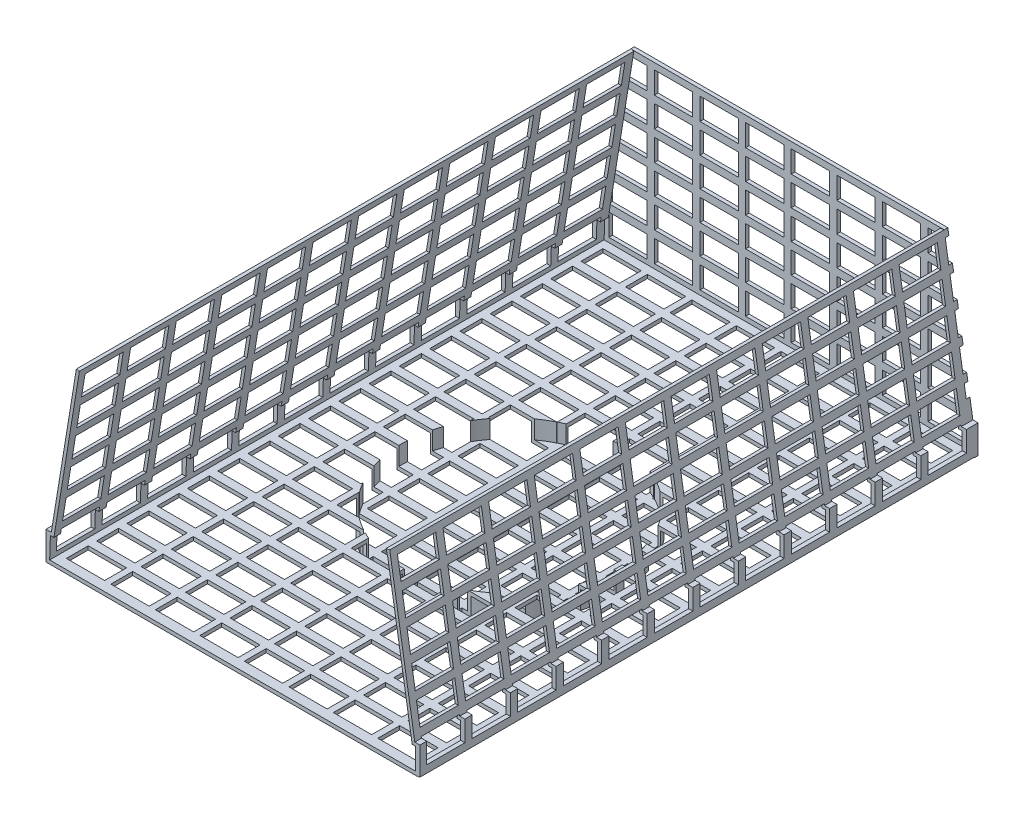
SolidWorks part; units mm, degrees
ref_plane "Front Plane" through (0, 0, 0) normal (0, 0, 1) x (1, 0, 0)
ref_plane "Top Plane" through (0, 0, 0) normal (0, 1, 0) x (1, 0, 0)
ref_plane "Right Plane" through (0, 0, 0) normal (1, 0, 0) x (0, 0, -1)
sketch "Sketch1" plane through (0, 0, 0) normal (0, 1, 0) x (1, 0, 0)
  line L1 (0, 0) -> (502.5, 0)
  line L2 (0, 0) -> (0, 760)
  line L3 (0, 760) -> (502.5, 760)
  line L4 (502.5, 0) -> (502.5, 760)
  dimension "D1" = 760
  dimension "D2" = 502.5
extrude "Boss-Extrude1" add sketch "Sketch1" against normal blind 5
sketch "Sketch2" plane through (0, 0, 0) normal (0, 1, 0) x (1, 0, 0)
  circle A0 centre (250.85, 380) radius 150
  dimension "D1" = 300
extrude "Boss-Extrude2" add sketch "Sketch2" against normal blind 30
sketch "Sketch3" plane through (0, 0, 0) normal (0, 1, 0) x (1, 0, 0)
  circle A0 centre (250.85, 380) radius 147.5
  dimension "D1" = 295
extrude "Cut-Extrude1" cut sketch "Sketch3" against normal blind 25
sketch "Sketch4" plane through (0, 0, -760) normal (0, 0, -1) x (-1, 0, 0)
  line L1 (-502.5, -5) -> (0, -5)
  line L2 (-502.5, -5) -> (-502.5, 245)
  line L3 (-502.5, 245) -> (0, 245)
  line L4 (0, -5) -> (0, 245)
  dimension "D1" = 250
extrude "Boss-Extrude3" add sketch "Sketch4" along normal blind 5
sketch "Sketch5" plane through (502.5, 0, 0) normal (1, 0, 0) x (0, 0, -1)
  line L1 (0, -5) -> (765, -5)
  line L2 (0, -5) -> (0, 245)
  line L3 (0, 245) -> (765, 245)
  line L4 (765, -5) -> (765, 245)
extrude "Boss-Extrude4" add sketch "Sketch5" along normal blind 5 and the other way blind 100
sketch "Sketch6" plane through (0, 0, 0) normal (-1, 0, 0) x (0, 0, 1)
  line L1 (0, -5) -> (-765, -5)
  line L2 (0, -5) -> (0, 245)
  line L3 (0, 245) -> (-765, 245)
  line L4 (-765, -5) -> (-765, 245)
extrude "Boss-Extrude5" add sketch "Sketch6" along normal blind 5 and the other way blind 100
sketch "Sketch7" plane through (507.5, 0, 0) normal (1, 0, 0) x (0, 0, -1)
  line L0 (71.6149, 235.9398) -> (124.1149, 235.9398)
  line L1 (9.1149, 235.9398) -> (61.6149, 235.9398)
  line L2 (9.1149, 235.9398) -> (9.1149, 205.9398)
  line L3 (9.1149, 205.9398) -> (61.6149, 205.9398)
  line L4 (61.6149, 235.9398) -> (61.6149, 205.9398)
  line L5 (71.6149, 235.9398) -> (71.6149, 205.9398)
  line L6 (71.6149, 205.9398) -> (124.1149, 205.9398)
  line L7 (124.1149, 235.9398) -> (124.1149, 205.9398)
  line L8 (134.1149, 235.9398) -> (186.6149, 235.9398)
  line L9 (134.1149, 235.9398) -> (134.1149, 205.9398)
  line L10 (134.1149, 205.9398) -> (186.6149, 205.9398)
  line L11 (186.6149, 235.9398) -> (186.6149, 205.9398)
  line L12 (196.6149, 235.9398) -> (249.1149, 235.9398)
  line L13 (196.6149, 235.9398) -> (196.6149, 205.9398)
  line L14 (196.6149, 205.9398) -> (249.1149, 205.9398)
  line L15 (249.1149, 235.9398) -> (249.1149, 205.9398)
  line L16 (259.1149, 235.9398) -> (311.6149, 235.9398)
  line L17 (259.1149, 235.9398) -> (259.1149, 205.9398)
  line L18 (259.1149, 205.9398) -> (311.6149, 205.9398)
  line L19 (311.6149, 235.9398) -> (311.6149, 205.9398)
  line L20 (321.6149, 235.9398) -> (374.1149, 235.9398)
  line L21 (321.6149, 235.9398) -> (321.6149, 205.9398)
  line L22 (321.6149, 205.9398) -> (374.1149, 205.9398)
  line L23 (374.1149, 235.9398) -> (374.1149, 205.9398)
  line L24 (384.1149, 235.9398) -> (436.6149, 235.9398)
  line L25 (384.1149, 235.9398) -> (384.1149, 205.9398)
  line L26 (384.1149, 205.9398) -> (436.6149, 205.9398)
  line L27 (436.6149, 235.9398) -> (436.6149, 205.9398)
  line L28 (446.6149, 235.9398) -> (499.1149, 235.9398)
  line L29 (446.6149, 235.9398) -> (446.6149, 205.9398)
  line L30 (446.6149, 205.9398) -> (499.1149, 205.9398)
  line L31 (499.1149, 235.9398) -> (499.1149, 205.9398)
  line L32 (509.1149, 235.9398) -> (561.6149, 235.9398)
  line L33 (509.1149, 235.9398) -> (509.1149, 205.9398)
  line L34 (509.1149, 205.9398) -> (561.6149, 205.9398)
  line L35 (561.6149, 235.9398) -> (561.6149, 205.9398)
  line L36 (571.6149, 235.9398) -> (624.1149, 235.9398)
  line L37 (571.6149, 235.9398) -> (571.6149, 205.9398)
  line L38 (571.6149, 205.9398) -> (624.1149, 205.9398)
  line L39 (624.1149, 235.9398) -> (624.1149, 205.9398)
  line L40 (634.1149, 235.9398) -> (686.6149, 235.9398)
  line L41 (634.1149, 235.9398) -> (634.1149, 205.9398)
  line L42 (634.1149, 205.9398) -> (686.6149, 205.9398)
  line L43 (686.6149, 235.9398) -> (686.6149, 205.9398)
  line L44 (696.6149, 235.9398) -> (749.1149, 235.9398)
  line L45 (696.6149, 235.9398) -> (696.6149, 205.9398)
  line L46 (696.6149, 205.9398) -> (749.1149, 205.9398)
  line L47 (749.1149, 235.9398) -> (749.1149, 205.9398)
  line L48 (71.6149, 195.9398) -> (124.1149, 195.9398)
  line L49 (9.1149, 195.9398) -> (61.6149, 195.9398)
  line L50 (9.1149, 195.9398) -> (9.1149, 165.9398)
  line L51 (9.1149, 165.9398) -> (61.6149, 165.9398)
  line L52 (61.6149, 195.9398) -> (61.6149, 165.9398)
  line L53 (71.6149, 195.9398) -> (71.6149, 165.9398)
  line L54 (71.6149, 165.9398) -> (124.1149, 165.9398)
  line L55 (124.1149, 195.9398) -> (124.1149, 165.9398)
  line L56 (134.1149, 195.9398) -> (186.6149, 195.9398)
  line L57 (134.1149, 195.9398) -> (134.1149, 165.9398)
  line L58 (134.1149, 165.9398) -> (186.6149, 165.9398)
  line L59 (186.6149, 195.9398) -> (186.6149, 165.9398)
  line L60 (196.6149, 195.9398) -> (249.1149, 195.9398)
  line L61 (196.6149, 195.9398) -> (196.6149, 165.9398)
  line L62 (196.6149, 165.9398) -> (249.1149, 165.9398)
  line L63 (249.1149, 195.9398) -> (249.1149, 165.9398)
  line L64 (259.1149, 195.9398) -> (311.6149, 195.9398)
  line L65 (259.1149, 195.9398) -> (259.1149, 165.9398)
  line L66 (259.1149, 165.9398) -> (311.6149, 165.9398)
  line L67 (311.6149, 195.9398) -> (311.6149, 165.9398)
  line L68 (321.6149, 195.9398) -> (374.1149, 195.9398)
  line L69 (321.6149, 195.9398) -> (321.6149, 165.9398)
  line L70 (321.6149, 165.9398) -> (374.1149, 165.9398)
  line L71 (374.1149, 195.9398) -> (374.1149, 165.9398)
  line L72 (384.1149, 195.9398) -> (436.6149, 195.9398)
  line L73 (384.1149, 195.9398) -> (384.1149, 165.9398)
  line L74 (384.1149, 165.9398) -> (436.6149, 165.9398)
  line L75 (436.6149, 195.9398) -> (436.6149, 165.9398)
  line L76 (446.6149, 195.9398) -> (499.1149, 195.9398)
  line L77 (446.6149, 195.9398) -> (446.6149, 165.9398)
  line L78 (446.6149, 165.9398) -> (499.1149, 165.9398)
  line L79 (499.1149, 195.9398) -> (499.1149, 165.9398)
  line L80 (509.1149, 195.9398) -> (561.6149, 195.9398)
  line L81 (509.1149, 195.9398) -> (509.1149, 165.9398)
  line L82 (509.1149, 165.9398) -> (561.6149, 165.9398)
  line L83 (561.6149, 195.9398) -> (561.6149, 165.9398)
  line L84 (571.6149, 195.9398) -> (624.1149, 195.9398)
  line L85 (571.6149, 195.9398) -> (571.6149, 165.9398)
  line L86 (571.6149, 165.9398) -> (624.1149, 165.9398)
  line L87 (624.1149, 195.9398) -> (624.1149, 165.9398)
  line L88 (634.1149, 195.9398) -> (686.6149, 195.9398)
  line L89 (634.1149, 195.9398) -> (634.1149, 165.9398)
  line L90 (634.1149, 165.9398) -> (686.6149, 165.9398)
  line L91 (686.6149, 195.9398) -> (686.6149, 165.9398)
  line L92 (696.6149, 195.9398) -> (749.1149, 195.9398)
  line L93 (696.6149, 195.9398) -> (696.6149, 165.9398)
  line L94 (696.6149, 165.9398) -> (749.1149, 165.9398)
  line L95 (749.1149, 195.9398) -> (749.1149, 165.9398)
  line L96 (71.6149, 155.9398) -> (124.1149, 155.9398)
  line L97 (9.1149, 155.9398) -> (61.6149, 155.9398)
  line L98 (9.1149, 155.9398) -> (9.1149, 125.9398)
  line L99 (9.1149, 125.9398) -> (61.6149, 125.9398)
  line L100 (61.6149, 155.9398) -> (61.6149, 125.9398)
  line L101 (71.6149, 155.9398) -> (71.6149, 125.9398)
  line L102 (71.6149, 125.9398) -> (124.1149, 125.9398)
  line L103 (124.1149, 155.9398) -> (124.1149, 125.9398)
  line L104 (134.1149, 155.9398) -> (186.6149, 155.9398)
  line L105 (134.1149, 155.9398) -> (134.1149, 125.9398)
  line L106 (134.1149, 125.9398) -> (186.6149, 125.9398)
  line L107 (186.6149, 155.9398) -> (186.6149, 125.9398)
  line L108 (196.6149, 155.9398) -> (249.1149, 155.9398)
  line L109 (196.6149, 155.9398) -> (196.6149, 125.9398)
  line L110 (196.6149, 125.9398) -> (249.1149, 125.9398)
  line L111 (249.1149, 155.9398) -> (249.1149, 125.9398)
  line L112 (259.1149, 155.9398) -> (311.6149, 155.9398)
  line L113 (259.1149, 155.9398) -> (259.1149, 125.9398)
  line L114 (259.1149, 125.9398) -> (311.6149, 125.9398)
  line L115 (311.6149, 155.9398) -> (311.6149, 125.9398)
  line L116 (321.6149, 155.9398) -> (374.1149, 155.9398)
  line L117 (321.6149, 155.9398) -> (321.6149, 125.9398)
  line L118 (321.6149, 125.9398) -> (374.1149, 125.9398)
  line L119 (374.1149, 155.9398) -> (374.1149, 125.9398)
  line L120 (384.1149, 155.9398) -> (436.6149, 155.9398)
  line L121 (384.1149, 155.9398) -> (384.1149, 125.9398)
  line L122 (384.1149, 125.9398) -> (436.6149, 125.9398)
  line L123 (436.6149, 155.9398) -> (436.6149, 125.9398)
  line L124 (446.6149, 155.9398) -> (499.1149, 155.9398)
  line L125 (446.6149, 155.9398) -> (446.6149, 125.9398)
  line L126 (446.6149, 125.9398) -> (499.1149, 125.9398)
  line L127 (499.1149, 155.9398) -> (499.1149, 125.9398)
  line L128 (509.1149, 155.9398) -> (561.6149, 155.9398)
  line L129 (509.1149, 155.9398) -> (509.1149, 125.9398)
  line L130 (509.1149, 125.9398) -> (561.6149, 125.9398)
  line L131 (561.6149, 155.9398) -> (561.6149, 125.9398)
  line L132 (571.6149, 155.9398) -> (624.1149, 155.9398)
  line L133 (571.6149, 155.9398) -> (571.6149, 125.9398)
  line L134 (571.6149, 125.9398) -> (624.1149, 125.9398)
  line L135 (624.1149, 155.9398) -> (624.1149, 125.9398)
  line L136 (634.1149, 155.9398) -> (686.6149, 155.9398)
  line L137 (634.1149, 155.9398) -> (634.1149, 125.9398)
  line L138 (634.1149, 125.9398) -> (686.6149, 125.9398)
  line L139 (686.6149, 155.9398) -> (686.6149, 125.9398)
  line L140 (696.6149, 155.9398) -> (749.1149, 155.9398)
  line L141 (696.6149, 155.9398) -> (696.6149, 125.9398)
  line L142 (696.6149, 125.9398) -> (749.1149, 125.9398)
  line L143 (749.1149, 155.9398) -> (749.1149, 125.9398)
  line L144 (71.6149, 115.9398) -> (124.1149, 115.9398)
  line L145 (9.1149, 115.9398) -> (61.6149, 115.9398)
  line L146 (9.1149, 115.9398) -> (9.1149, 85.9398)
  line L147 (9.1149, 85.9398) -> (61.6149, 85.9398)
  line L148 (61.6149, 115.9398) -> (61.6149, 85.9398)
  line L149 (71.6149, 115.9398) -> (71.6149, 85.9398)
  line L150 (71.6149, 85.9398) -> (124.1149, 85.9398)
  line L151 (124.1149, 115.9398) -> (124.1149, 85.9398)
  line L152 (134.1149, 115.9398) -> (186.6149, 115.9398)
  line L153 (134.1149, 115.9398) -> (134.1149, 85.9398)
  line L154 (134.1149, 85.9398) -> (186.6149, 85.9398)
  line L155 (186.6149, 115.9398) -> (186.6149, 85.9398)
  line L156 (196.6149, 115.9398) -> (249.1149, 115.9398)
  line L157 (196.6149, 115.9398) -> (196.6149, 85.9398)
  line L158 (196.6149, 85.9398) -> (249.1149, 85.9398)
  line L159 (249.1149, 115.9398) -> (249.1149, 85.9398)
  line L160 (259.1149, 115.9398) -> (311.6149, 115.9398)
  line L161 (259.1149, 115.9398) -> (259.1149, 85.9398)
  line L162 (259.1149, 85.9398) -> (311.6149, 85.9398)
  line L163 (311.6149, 115.9398) -> (311.6149, 85.9398)
  line L164 (321.6149, 115.9398) -> (374.1149, 115.9398)
  line L165 (321.6149, 115.9398) -> (321.6149, 85.9398)
  line L166 (321.6149, 85.9398) -> (374.1149, 85.9398)
  line L167 (374.1149, 115.9398) -> (374.1149, 85.9398)
  line L168 (384.1149, 115.9398) -> (436.6149, 115.9398)
  line L169 (384.1149, 115.9398) -> (384.1149, 85.9398)
  line L170 (384.1149, 85.9398) -> (436.6149, 85.9398)
  line L171 (436.6149, 115.9398) -> (436.6149, 85.9398)
  line L172 (446.6149, 115.9398) -> (499.1149, 115.9398)
  line L173 (446.6149, 115.9398) -> (446.6149, 85.9398)
  line L174 (446.6149, 85.9398) -> (499.1149, 85.9398)
  line L175 (499.1149, 115.9398) -> (499.1149, 85.9398)
  line L176 (509.1149, 115.9398) -> (561.6149, 115.9398)
  line L177 (509.1149, 115.9398) -> (509.1149, 85.9398)
  line L178 (509.1149, 85.9398) -> (561.6149, 85.9398)
  line L179 (561.6149, 115.9398) -> (561.6149, 85.9398)
  line L180 (571.6149, 115.9398) -> (624.1149, 115.9398)
  line L181 (571.6149, 115.9398) -> (571.6149, 85.9398)
  line L182 (571.6149, 85.9398) -> (624.1149, 85.9398)
  line L183 (624.1149, 115.9398) -> (624.1149, 85.9398)
  line L184 (634.1149, 115.9398) -> (686.6149, 115.9398)
  line L185 (634.1149, 115.9398) -> (634.1149, 85.9398)
  line L186 (634.1149, 85.9398) -> (686.6149, 85.9398)
  line L187 (686.6149, 115.9398) -> (686.6149, 85.9398)
  line L188 (696.6149, 115.9398) -> (749.1149, 115.9398)
  line L189 (696.6149, 115.9398) -> (696.6149, 85.9398)
  line L190 (696.6149, 85.9398) -> (749.1149, 85.9398)
  line L191 (749.1149, 115.9398) -> (749.1149, 85.9398)
  line L192 (71.6149, 75.9398) -> (124.1149, 75.9398)
  line L193 (9.1149, 75.9398) -> (61.6149, 75.9398)
  line L194 (9.1149, 75.9398) -> (9.1149, 45.9398)
  line L195 (9.1149, 45.9398) -> (61.6149, 45.9398)
  line L196 (61.6149, 75.9398) -> (61.6149, 45.9398)
  line L197 (71.6149, 75.9398) -> (71.6149, 45.9398)
  line L198 (71.6149, 45.9398) -> (124.1149, 45.9398)
  line L199 (124.1149, 75.9398) -> (124.1149, 45.9398)
  line L200 (134.1149, 75.9398) -> (186.6149, 75.9398)
  line L201 (134.1149, 75.9398) -> (134.1149, 45.9398)
  line L202 (134.1149, 45.9398) -> (186.6149, 45.9398)
  line L203 (186.6149, 75.9398) -> (186.6149, 45.9398)
  line L204 (196.6149, 75.9398) -> (249.1149, 75.9398)
  line L205 (196.6149, 75.9398) -> (196.6149, 45.9398)
  line L206 (196.6149, 45.9398) -> (249.1149, 45.9398)
  line L207 (249.1149, 75.9398) -> (249.1149, 45.9398)
  line L208 (259.1149, 75.9398) -> (311.6149, 75.9398)
  line L209 (259.1149, 75.9398) -> (259.1149, 45.9398)
  line L210 (259.1149, 45.9398) -> (311.6149, 45.9398)
  line L211 (311.6149, 75.9398) -> (311.6149, 45.9398)
  line L212 (321.6149, 75.9398) -> (374.1149, 75.9398)
  line L213 (321.6149, 75.9398) -> (321.6149, 45.9398)
  line L214 (321.6149, 45.9398) -> (374.1149, 45.9398)
  line L215 (374.1149, 75.9398) -> (374.1149, 45.9398)
  line L216 (384.1149, 75.9398) -> (436.6149, 75.9398)
  line L217 (384.1149, 75.9398) -> (384.1149, 45.9398)
  line L218 (384.1149, 45.9398) -> (436.6149, 45.9398)
  line L219 (436.6149, 75.9398) -> (436.6149, 45.9398)
  line L220 (446.6149, 75.9398) -> (499.1149, 75.9398)
  line L221 (446.6149, 75.9398) -> (446.6149, 45.9398)
  line L222 (446.6149, 45.9398) -> (499.1149, 45.9398)
  line L223 (499.1149, 75.9398) -> (499.1149, 45.9398)
  line L224 (509.1149, 75.9398) -> (561.6149, 75.9398)
  line L225 (509.1149, 75.9398) -> (509.1149, 45.9398)
  line L226 (509.1149, 45.9398) -> (561.6149, 45.9398)
  line L227 (561.6149, 75.9398) -> (561.6149, 45.9398)
  line L228 (571.6149, 75.9398) -> (624.1149, 75.9398)
  line L229 (571.6149, 75.9398) -> (571.6149, 45.9398)
  line L230 (571.6149, 45.9398) -> (624.1149, 45.9398)
  line L231 (624.1149, 75.9398) -> (624.1149, 45.9398)
  line L232 (634.1149, 75.9398) -> (686.6149, 75.9398)
  line L233 (634.1149, 75.9398) -> (634.1149, 45.9398)
  line L234 (634.1149, 45.9398) -> (686.6149, 45.9398)
  line L235 (686.6149, 75.9398) -> (686.6149, 45.9398)
  line L236 (696.6149, 75.9398) -> (749.1149, 75.9398)
  line L237 (696.6149, 75.9398) -> (696.6149, 45.9398)
  line L238 (696.6149, 45.9398) -> (749.1149, 45.9398)
  line L239 (749.1149, 75.9398) -> (749.1149, 45.9398)
  line L240 (71.6149, 35.9398) -> (124.1149, 35.9398)
  line L241 (9.1149, 35.9398) -> (61.6149, 35.9398)
  line L242 (9.1149, 35.9398) -> (9.1149, 5.9398)
  line L243 (9.1149, 5.9398) -> (61.6149, 5.9398)
  line L244 (61.6149, 35.9398) -> (61.6149, 5.9398)
  line L245 (71.6149, 35.9398) -> (71.6149, 5.9398)
  line L246 (71.6149, 5.9398) -> (124.1149, 5.9398)
  line L247 (124.1149, 35.9398) -> (124.1149, 5.9398)
  line L248 (134.1149, 35.9398) -> (186.6149, 35.9398)
  line L249 (134.1149, 35.9398) -> (134.1149, 5.9398)
  line L250 (134.1149, 5.9398) -> (186.6149, 5.9398)
  line L251 (186.6149, 35.9398) -> (186.6149, 5.9398)
  line L252 (196.6149, 35.9398) -> (249.1149, 35.9398)
  line L253 (196.6149, 35.9398) -> (196.6149, 5.9398)
  line L254 (196.6149, 5.9398) -> (249.1149, 5.9398)
  line L255 (249.1149, 35.9398) -> (249.1149, 5.9398)
  line L256 (259.1149, 35.9398) -> (311.6149, 35.9398)
  line L257 (259.1149, 35.9398) -> (259.1149, 5.9398)
  line L258 (259.1149, 5.9398) -> (311.6149, 5.9398)
  line L259 (311.6149, 35.9398) -> (311.6149, 5.9398)
  line L260 (321.6149, 35.9398) -> (374.1149, 35.9398)
  line L261 (321.6149, 35.9398) -> (321.6149, 5.9398)
  line L262 (321.6149, 5.9398) -> (374.1149, 5.9398)
  line L263 (374.1149, 35.9398) -> (374.1149, 5.9398)
  line L264 (384.1149, 35.9398) -> (436.6149, 35.9398)
  line L265 (384.1149, 35.9398) -> (384.1149, 5.9398)
  line L266 (384.1149, 5.9398) -> (436.6149, 5.9398)
  line L267 (436.6149, 35.9398) -> (436.6149, 5.9398)
  line L268 (446.6149, 35.9398) -> (499.1149, 35.9398)
  line L269 (446.6149, 35.9398) -> (446.6149, 5.9398)
  line L270 (446.6149, 5.9398) -> (499.1149, 5.9398)
  line L271 (499.1149, 35.9398) -> (499.1149, 5.9398)
  line L272 (509.1149, 35.9398) -> (561.6149, 35.9398)
  line L273 (509.1149, 35.9398) -> (509.1149, 5.9398)
  line L274 (509.1149, 5.9398) -> (561.6149, 5.9398)
  line L275 (561.6149, 35.9398) -> (561.6149, 5.9398)
  line L276 (571.6149, 35.9398) -> (624.1149, 35.9398)
  line L277 (571.6149, 35.9398) -> (571.6149, 5.9398)
  line L278 (571.6149, 5.9398) -> (624.1149, 5.9398)
  line L279 (624.1149, 35.9398) -> (624.1149, 5.9398)
  line L280 (634.1149, 35.9398) -> (686.6149, 35.9398)
  line L281 (634.1149, 35.9398) -> (634.1149, 5.9398)
  line L282 (634.1149, 5.9398) -> (686.6149, 5.9398)
  line L283 (686.6149, 35.9398) -> (686.6149, 5.9398)
  line L284 (696.6149, 35.9398) -> (749.1149, 35.9398)
  line L285 (696.6149, 35.9398) -> (696.6149, 5.9398)
  line L286 (696.6149, 5.9398) -> (749.1149, 5.9398)
  line L287 (749.1149, 35.9398) -> (749.1149, 5.9398)
  dimension "D1" = 12
  dimension "D2" = 52.5
  dimension "D3" = 10
  dimension "D5" = 30
  dimension "D6" = 10
  dimension "D4" = 6
extrude "Cut-Extrude2" cut sketch "Sketch7" against normal through all
sketch "Sketch8" plane through (0, 0, -765) normal (0, 0, -1) x (-1, 0, 0)
  line L0 (-433.8888, 206.2331) -> (-381.3888, 206.2331)
  line L1 (-496.3888, 206.2331) -> (-443.8888, 206.2331)
  line L2 (-496.3888, 206.2331) -> (-496.3888, 236.2331)
  line L3 (-496.3888, 236.2331) -> (-443.8888, 236.2331)
  line L4 (-443.8888, 206.2331) -> (-443.8888, 236.2331)
  line L5 (-433.8888, 206.2331) -> (-433.8888, 236.2331)
  line L6 (-433.8888, 236.2331) -> (-381.3888, 236.2331)
  line L7 (-381.3888, 206.2331) -> (-381.3888, 236.2331)
  line L8 (-371.3888, 206.2331) -> (-318.8888, 206.2331)
  line L9 (-371.3888, 206.2331) -> (-371.3888, 236.2331)
  line L10 (-371.3888, 236.2331) -> (-318.8888, 236.2331)
  line L11 (-318.8888, 206.2331) -> (-318.8888, 236.2331)
  line L12 (-308.8888, 206.2331) -> (-256.3888, 206.2331)
  line L13 (-308.8888, 206.2331) -> (-308.8888, 236.2331)
  line L14 (-308.8888, 236.2331) -> (-256.3888, 236.2331)
  line L15 (-256.3888, 206.2331) -> (-256.3888, 236.2331)
  line L16 (-246.3888, 206.2331) -> (-193.8888, 206.2331)
  line L17 (-246.3888, 206.2331) -> (-246.3888, 236.2331)
  line L18 (-246.3888, 236.2331) -> (-193.8888, 236.2331)
  line L19 (-193.8888, 206.2331) -> (-193.8888, 236.2331)
  line L20 (-183.8888, 206.2331) -> (-131.3888, 206.2331)
  line L21 (-183.8888, 206.2331) -> (-183.8888, 236.2331)
  line L22 (-183.8888, 236.2331) -> (-131.3888, 236.2331)
  line L23 (-131.3888, 206.2331) -> (-131.3888, 236.2331)
  line L24 (-121.3888, 206.2331) -> (-68.8888, 206.2331)
  line L25 (-121.3888, 206.2331) -> (-121.3888, 236.2331)
  line L26 (-121.3888, 236.2331) -> (-68.8888, 236.2331)
  line L27 (-68.8888, 206.2331) -> (-68.8888, 236.2331)
  line L28 (-58.8888, 206.2331) -> (-6.3888, 206.2331)
  line L29 (-58.8888, 206.2331) -> (-58.8888, 236.2331)
  line L30 (-58.8888, 236.2331) -> (-6.3888, 236.2331)
  line L31 (-6.3888, 206.2331) -> (-6.3888, 236.2331)
  line L32 (-433.8888, 166.2331) -> (-381.3888, 166.2331)
  line L33 (-496.3888, 166.2331) -> (-443.8888, 166.2331)
  line L34 (-496.3888, 166.2331) -> (-496.3888, 196.2331)
  line L35 (-496.3888, 196.2331) -> (-443.8888, 196.2331)
  line L36 (-443.8888, 166.2331) -> (-443.8888, 196.2331)
  line L37 (-433.8888, 166.2331) -> (-433.8888, 196.2331)
  line L38 (-433.8888, 196.2331) -> (-381.3888, 196.2331)
  line L39 (-381.3888, 166.2331) -> (-381.3888, 196.2331)
  line L40 (-371.3888, 166.2331) -> (-318.8888, 166.2331)
  line L41 (-371.3888, 166.2331) -> (-371.3888, 196.2331)
  line L42 (-371.3888, 196.2331) -> (-318.8888, 196.2331)
  line L43 (-318.8888, 166.2331) -> (-318.8888, 196.2331)
  line L44 (-308.8888, 166.2331) -> (-256.3888, 166.2331)
  line L45 (-308.8888, 166.2331) -> (-308.8888, 196.2331)
  line L46 (-308.8888, 196.2331) -> (-256.3888, 196.2331)
  line L47 (-256.3888, 166.2331) -> (-256.3888, 196.2331)
  line L48 (-246.3888, 166.2331) -> (-193.8888, 166.2331)
  line L49 (-246.3888, 166.2331) -> (-246.3888, 196.2331)
  line L50 (-246.3888, 196.2331) -> (-193.8888, 196.2331)
  line L51 (-193.8888, 166.2331) -> (-193.8888, 196.2331)
  line L52 (-183.8888, 166.2331) -> (-131.3888, 166.2331)
  line L53 (-183.8888, 166.2331) -> (-183.8888, 196.2331)
  line L54 (-183.8888, 196.2331) -> (-131.3888, 196.2331)
  line L55 (-131.3888, 166.2331) -> (-131.3888, 196.2331)
  line L56 (-121.3888, 166.2331) -> (-68.8888, 166.2331)
  line L57 (-121.3888, 166.2331) -> (-121.3888, 196.2331)
  line L58 (-121.3888, 196.2331) -> (-68.8888, 196.2331)
  line L59 (-68.8888, 166.2331) -> (-68.8888, 196.2331)
  line L60 (-58.8888, 166.2331) -> (-6.3888, 166.2331)
  line L61 (-58.8888, 166.2331) -> (-58.8888, 196.2331)
  line L62 (-58.8888, 196.2331) -> (-6.3888, 196.2331)
  line L63 (-6.3888, 166.2331) -> (-6.3888, 196.2331)
  line L64 (-433.8888, 126.2331) -> (-381.3888, 126.2331)
  line L65 (-496.3888, 126.2331) -> (-443.8888, 126.2331)
  line L66 (-496.3888, 126.2331) -> (-496.3888, 156.2331)
  line L67 (-496.3888, 156.2331) -> (-443.8888, 156.2331)
  line L68 (-443.8888, 126.2331) -> (-443.8888, 156.2331)
  line L69 (-433.8888, 126.2331) -> (-433.8888, 156.2331)
  line L70 (-433.8888, 156.2331) -> (-381.3888, 156.2331)
  line L71 (-381.3888, 126.2331) -> (-381.3888, 156.2331)
  line L72 (-371.3888, 126.2331) -> (-318.8888, 126.2331)
  line L73 (-371.3888, 126.2331) -> (-371.3888, 156.2331)
  line L74 (-371.3888, 156.2331) -> (-318.8888, 156.2331)
  line L75 (-318.8888, 126.2331) -> (-318.8888, 156.2331)
  line L76 (-308.8888, 126.2331) -> (-256.3888, 126.2331)
  line L77 (-308.8888, 126.2331) -> (-308.8888, 156.2331)
  line L78 (-308.8888, 156.2331) -> (-256.3888, 156.2331)
  line L79 (-256.3888, 126.2331) -> (-256.3888, 156.2331)
  line L80 (-246.3888, 126.2331) -> (-193.8888, 126.2331)
  line L81 (-246.3888, 126.2331) -> (-246.3888, 156.2331)
  line L82 (-246.3888, 156.2331) -> (-193.8888, 156.2331)
  line L83 (-193.8888, 126.2331) -> (-193.8888, 156.2331)
  line L84 (-183.8888, 126.2331) -> (-131.3888, 126.2331)
  line L85 (-183.8888, 126.2331) -> (-183.8888, 156.2331)
  line L86 (-183.8888, 156.2331) -> (-131.3888, 156.2331)
  line L87 (-131.3888, 126.2331) -> (-131.3888, 156.2331)
  line L88 (-121.3888, 126.2331) -> (-68.8888, 126.2331)
  line L89 (-121.3888, 126.2331) -> (-121.3888, 156.2331)
  line L90 (-121.3888, 156.2331) -> (-68.8888, 156.2331)
  line L91 (-68.8888, 126.2331) -> (-68.8888, 156.2331)
  line L92 (-58.8888, 126.2331) -> (-6.3888, 126.2331)
  line L93 (-58.8888, 126.2331) -> (-58.8888, 156.2331)
  line L94 (-58.8888, 156.2331) -> (-6.3888, 156.2331)
  line L95 (-6.3888, 126.2331) -> (-6.3888, 156.2331)
  line L96 (-433.8888, 86.2331) -> (-381.3888, 86.2331)
  line L97 (-496.3888, 86.2331) -> (-443.8888, 86.2331)
  line L98 (-496.3888, 86.2331) -> (-496.3888, 116.2331)
  line L99 (-496.3888, 116.2331) -> (-443.8888, 116.2331)
  line L100 (-443.8888, 86.2331) -> (-443.8888, 116.2331)
  line L101 (-433.8888, 86.2331) -> (-433.8888, 116.2331)
  line L102 (-433.8888, 116.2331) -> (-381.3888, 116.2331)
  line L103 (-381.3888, 86.2331) -> (-381.3888, 116.2331)
  line L104 (-371.3888, 86.2331) -> (-318.8888, 86.2331)
  line L105 (-371.3888, 86.2331) -> (-371.3888, 116.2331)
  line L106 (-371.3888, 116.2331) -> (-318.8888, 116.2331)
  line L107 (-318.8888, 86.2331) -> (-318.8888, 116.2331)
  line L108 (-308.8888, 86.2331) -> (-256.3888, 86.2331)
  line L109 (-308.8888, 86.2331) -> (-308.8888, 116.2331)
  line L110 (-308.8888, 116.2331) -> (-256.3888, 116.2331)
  line L111 (-256.3888, 86.2331) -> (-256.3888, 116.2331)
  line L112 (-246.3888, 86.2331) -> (-193.8888, 86.2331)
  line L113 (-246.3888, 86.2331) -> (-246.3888, 116.2331)
  line L114 (-246.3888, 116.2331) -> (-193.8888, 116.2331)
  line L115 (-193.8888, 86.2331) -> (-193.8888, 116.2331)
  line L116 (-183.8888, 86.2331) -> (-131.3888, 86.2331)
  line L117 (-183.8888, 86.2331) -> (-183.8888, 116.2331)
  line L118 (-183.8888, 116.2331) -> (-131.3888, 116.2331)
  line L119 (-131.3888, 86.2331) -> (-131.3888, 116.2331)
  line L120 (-121.3888, 86.2331) -> (-68.8888, 86.2331)
  line L121 (-121.3888, 86.2331) -> (-121.3888, 116.2331)
  line L122 (-121.3888, 116.2331) -> (-68.8888, 116.2331)
  line L123 (-68.8888, 86.2331) -> (-68.8888, 116.2331)
  line L124 (-58.8888, 86.2331) -> (-6.3888, 86.2331)
  line L125 (-58.8888, 86.2331) -> (-58.8888, 116.2331)
  line L126 (-58.8888, 116.2331) -> (-6.3888, 116.2331)
  line L127 (-6.3888, 86.2331) -> (-6.3888, 116.2331)
  line L128 (-433.8888, 46.2331) -> (-381.3888, 46.2331)
  line L129 (-496.3888, 46.2331) -> (-443.8888, 46.2331)
  line L130 (-496.3888, 46.2331) -> (-496.3888, 76.2331)
  line L131 (-496.3888, 76.2331) -> (-443.8888, 76.2331)
  line L132 (-443.8888, 46.2331) -> (-443.8888, 76.2331)
  line L133 (-433.8888, 46.2331) -> (-433.8888, 76.2331)
  line L134 (-433.8888, 76.2331) -> (-381.3888, 76.2331)
  line L135 (-381.3888, 46.2331) -> (-381.3888, 76.2331)
  line L136 (-371.3888, 46.2331) -> (-318.8888, 46.2331)
  line L137 (-371.3888, 46.2331) -> (-371.3888, 76.2331)
  line L138 (-371.3888, 76.2331) -> (-318.8888, 76.2331)
  line L139 (-318.8888, 46.2331) -> (-318.8888, 76.2331)
  line L140 (-308.8888, 46.2331) -> (-256.3888, 46.2331)
  line L141 (-308.8888, 46.2331) -> (-308.8888, 76.2331)
  line L142 (-308.8888, 76.2331) -> (-256.3888, 76.2331)
  line L143 (-256.3888, 46.2331) -> (-256.3888, 76.2331)
  line L144 (-246.3888, 46.2331) -> (-193.8888, 46.2331)
  line L145 (-246.3888, 46.2331) -> (-246.3888, 76.2331)
  line L146 (-246.3888, 76.2331) -> (-193.8888, 76.2331)
  line L147 (-193.8888, 46.2331) -> (-193.8888, 76.2331)
  line L148 (-183.8888, 46.2331) -> (-131.3888, 46.2331)
  line L149 (-183.8888, 46.2331) -> (-183.8888, 76.2331)
  line L150 (-183.8888, 76.2331) -> (-131.3888, 76.2331)
  line L151 (-131.3888, 46.2331) -> (-131.3888, 76.2331)
  line L152 (-121.3888, 46.2331) -> (-68.8888, 46.2331)
  line L153 (-121.3888, 46.2331) -> (-121.3888, 76.2331)
  line L154 (-121.3888, 76.2331) -> (-68.8888, 76.2331)
  line L155 (-68.8888, 46.2331) -> (-68.8888, 76.2331)
  line L156 (-58.8888, 46.2331) -> (-6.3888, 46.2331)
  line L157 (-58.8888, 46.2331) -> (-58.8888, 76.2331)
  line L158 (-58.8888, 76.2331) -> (-6.3888, 76.2331)
  line L159 (-6.3888, 46.2331) -> (-6.3888, 76.2331)
  line L160 (-433.8888, 6.2331) -> (-381.3888, 6.2331)
  line L161 (-496.3888, 6.2331) -> (-443.8888, 6.2331)
  line L162 (-496.3888, 6.2331) -> (-496.3888, 36.2331)
  line L163 (-496.3888, 36.2331) -> (-443.8888, 36.2331)
  line L164 (-443.8888, 6.2331) -> (-443.8888, 36.2331)
  line L165 (-433.8888, 6.2331) -> (-433.8888, 36.2331)
  line L166 (-433.8888, 36.2331) -> (-381.3888, 36.2331)
  line L167 (-381.3888, 6.2331) -> (-381.3888, 36.2331)
  line L168 (-371.3888, 6.2331) -> (-318.8888, 6.2331)
  line L169 (-371.3888, 6.2331) -> (-371.3888, 36.2331)
  line L170 (-371.3888, 36.2331) -> (-318.8888, 36.2331)
  line L171 (-318.8888, 6.2331) -> (-318.8888, 36.2331)
  line L172 (-308.8888, 6.2331) -> (-256.3888, 6.2331)
  line L173 (-308.8888, 6.2331) -> (-308.8888, 36.2331)
  line L174 (-308.8888, 36.2331) -> (-256.3888, 36.2331)
  line L175 (-256.3888, 6.2331) -> (-256.3888, 36.2331)
  line L176 (-246.3888, 6.2331) -> (-193.8888, 6.2331)
  line L177 (-246.3888, 6.2331) -> (-246.3888, 36.2331)
  line L178 (-246.3888, 36.2331) -> (-193.8888, 36.2331)
  line L179 (-193.8888, 6.2331) -> (-193.8888, 36.2331)
  line L180 (-183.8888, 6.2331) -> (-131.3888, 6.2331)
  line L181 (-183.8888, 6.2331) -> (-183.8888, 36.2331)
  line L182 (-183.8888, 36.2331) -> (-131.3888, 36.2331)
  line L183 (-131.3888, 6.2331) -> (-131.3888, 36.2331)
  line L184 (-121.3888, 6.2331) -> (-68.8888, 6.2331)
  line L185 (-121.3888, 6.2331) -> (-121.3888, 36.2331)
  line L186 (-121.3888, 36.2331) -> (-68.8888, 36.2331)
  line L187 (-68.8888, 6.2331) -> (-68.8888, 36.2331)
  line L188 (-58.8888, 6.2331) -> (-6.3888, 6.2331)
  line L189 (-58.8888, 6.2331) -> (-58.8888, 36.2331)
  line L190 (-58.8888, 36.2331) -> (-6.3888, 36.2331)
  line L191 (-6.3888, 6.2331) -> (-6.3888, 36.2331)
  dimension "D1" = 30
  dimension "D2" = 52.5
  dimension "D5" = 10
  dimension "D3" = 8
  dimension "D4" = 6
extrude "Cut-Extrude3" cut sketch "Sketch8" against normal blind 5
sketch "Sketch9" plane through (0, 0, 0) normal (0, 1, 0) x (1, 0, 0)
  line L0 (70.5965, 718.7907) -> (123.0965, 718.7907)
  line L1 (9.5965, 718.7907) -> (62.0965, 718.7907)
  line L2 (9.5965, 718.7907) -> (9.5965, 748.7907)
  line L3 (9.5965, 748.7907) -> (62.0965, 748.7907)
  line L4 (62.0965, 718.7907) -> (62.0965, 748.7907)
  line L5 (70.5965, 718.7907) -> (70.5965, 748.7907)
  line L6 (70.5965, 748.7907) -> (123.0965, 748.7907)
  line L7 (123.0965, 718.7907) -> (123.0965, 748.7907)
  line L8 (131.5965, 718.7907) -> (184.0965, 718.7907)
  line L9 (131.5965, 718.7907) -> (131.5965, 748.7907)
  line L10 (131.5965, 748.7907) -> (184.0965, 748.7907)
  line L11 (184.0965, 718.7907) -> (184.0965, 748.7907)
  line L12 (192.5965, 718.7907) -> (245.0965, 718.7907)
  line L13 (192.5965, 718.7907) -> (192.5965, 748.7907)
  line L14 (192.5965, 748.7907) -> (245.0965, 748.7907)
  line L15 (245.0965, 718.7907) -> (245.0965, 748.7907)
  line L16 (253.5965, 718.7907) -> (306.0965, 718.7907)
  line L17 (253.5965, 718.7907) -> (253.5965, 748.7907)
  line L18 (253.5965, 748.7907) -> (306.0965, 748.7907)
  line L19 (306.0965, 718.7907) -> (306.0965, 748.7907)
  line L20 (314.5965, 718.7907) -> (367.0965, 718.7907)
  line L21 (314.5965, 718.7907) -> (314.5965, 748.7907)
  line L22 (314.5965, 748.7907) -> (367.0965, 748.7907)
  line L23 (367.0965, 718.7907) -> (367.0965, 748.7907)
  line L24 (375.5965, 718.7907) -> (428.0965, 718.7907)
  line L25 (375.5965, 718.7907) -> (375.5965, 748.7907)
  line L26 (375.5965, 748.7907) -> (428.0965, 748.7907)
  line L27 (428.0965, 718.7907) -> (428.0965, 748.7907)
  line L28 (436.5965, 718.7907) -> (489.0965, 718.7907)
  line L29 (436.5965, 718.7907) -> (436.5965, 748.7907)
  line L30 (436.5965, 748.7907) -> (489.0965, 748.7907)
  line L31 (489.0965, 718.7907) -> (489.0965, 748.7907)
  line L32 (70.5965, 677.2907) -> (123.0965, 677.2907)
  line L33 (9.5965, 677.2907) -> (62.0965, 677.2907)
  line L34 (9.5965, 677.2907) -> (9.5965, 707.2907)
  line L35 (9.5965, 707.2907) -> (62.0965, 707.2907)
  line L36 (62.0965, 677.2907) -> (62.0965, 707.2907)
  line L37 (70.5965, 677.2907) -> (70.5965, 707.2907)
  line L38 (70.5965, 707.2907) -> (123.0965, 707.2907)
  line L39 (123.0965, 677.2907) -> (123.0965, 707.2907)
  line L40 (131.5965, 677.2907) -> (184.0965, 677.2907)
  line L41 (131.5965, 677.2907) -> (131.5965, 707.2907)
  line L42 (131.5965, 707.2907) -> (184.0965, 707.2907)
  line L43 (184.0965, 677.2907) -> (184.0965, 707.2907)
  line L44 (192.5965, 677.2907) -> (245.0965, 677.2907)
  line L45 (192.5965, 677.2907) -> (192.5965, 707.2907)
  line L46 (192.5965, 707.2907) -> (245.0965, 707.2907)
  line L47 (245.0965, 677.2907) -> (245.0965, 707.2907)
  line L48 (253.5965, 677.2907) -> (306.0965, 677.2907)
  line L49 (253.5965, 677.2907) -> (253.5965, 707.2907)
  line L50 (253.5965, 707.2907) -> (306.0965, 707.2907)
  line L51 (306.0965, 677.2907) -> (306.0965, 707.2907)
  line L52 (314.5965, 677.2907) -> (367.0965, 677.2907)
  line L53 (314.5965, 677.2907) -> (314.5965, 707.2907)
  line L54 (314.5965, 707.2907) -> (367.0965, 707.2907)
  line L55 (367.0965, 677.2907) -> (367.0965, 707.2907)
  line L56 (375.5965, 677.2907) -> (428.0965, 677.2907)
  line L57 (375.5965, 677.2907) -> (375.5965, 707.2907)
  line L58 (375.5965, 707.2907) -> (428.0965, 707.2907)
  line L59 (428.0965, 677.2907) -> (428.0965, 707.2907)
  line L60 (436.5965, 677.2907) -> (489.0965, 677.2907)
  line L61 (436.5965, 677.2907) -> (436.5965, 707.2907)
  line L62 (436.5965, 707.2907) -> (489.0965, 707.2907)
  line L63 (489.0965, 677.2907) -> (489.0965, 707.2907)
  line L64 (70.5965, 635.7907) -> (123.0965, 635.7907)
  line L65 (9.5965, 635.7907) -> (62.0965, 635.7907)
  line L66 (9.5965, 635.7907) -> (9.5965, 665.7907)
  line L67 (9.5965, 665.7907) -> (62.0965, 665.7907)
  line L68 (62.0965, 635.7907) -> (62.0965, 665.7907)
  line L69 (70.5965, 635.7907) -> (70.5965, 665.7907)
  line L70 (70.5965, 665.7907) -> (123.0965, 665.7907)
  line L71 (123.0965, 635.7907) -> (123.0965, 665.7907)
  line L72 (131.5965, 635.7907) -> (184.0965, 635.7907)
  line L73 (131.5965, 635.7907) -> (131.5965, 665.7907)
  line L74 (131.5965, 665.7907) -> (184.0965, 665.7907)
  line L75 (184.0965, 635.7907) -> (184.0965, 665.7907)
  line L76 (192.5965, 635.7907) -> (245.0965, 635.7907)
  line L77 (192.5965, 635.7907) -> (192.5965, 665.7907)
  line L78 (192.5965, 665.7907) -> (245.0965, 665.7907)
  line L79 (245.0965, 635.7907) -> (245.0965, 665.7907)
  line L80 (253.5965, 635.7907) -> (306.0965, 635.7907)
  line L81 (253.5965, 635.7907) -> (253.5965, 665.7907)
  line L82 (253.5965, 665.7907) -> (306.0965, 665.7907)
  line L83 (306.0965, 635.7907) -> (306.0965, 665.7907)
  line L84 (314.5965, 635.7907) -> (367.0965, 635.7907)
  line L85 (314.5965, 635.7907) -> (314.5965, 665.7907)
  line L86 (314.5965, 665.7907) -> (367.0965, 665.7907)
  line L87 (367.0965, 635.7907) -> (367.0965, 665.7907)
  line L88 (375.5965, 635.7907) -> (428.0965, 635.7907)
  line L89 (375.5965, 635.7907) -> (375.5965, 665.7907)
  line L90 (375.5965, 665.7907) -> (428.0965, 665.7907)
  line L91 (428.0965, 635.7907) -> (428.0965, 665.7907)
  line L92 (436.5965, 635.7907) -> (489.0965, 635.7907)
  line L93 (436.5965, 635.7907) -> (436.5965, 665.7907)
  line L94 (436.5965, 665.7907) -> (489.0965, 665.7907)
  line L95 (489.0965, 635.7907) -> (489.0965, 665.7907)
  line L96 (70.5965, 594.2907) -> (123.0965, 594.2907)
  line L97 (9.5965, 594.2907) -> (62.0965, 594.2907)
  line L98 (9.5965, 594.2907) -> (9.5965, 624.2907)
  line L99 (9.5965, 624.2907) -> (62.0965, 624.2907)
  line L100 (62.0965, 594.2907) -> (62.0965, 624.2907)
  line L101 (70.5965, 594.2907) -> (70.5965, 624.2907)
  line L102 (70.5965, 624.2907) -> (123.0965, 624.2907)
  line L103 (123.0965, 594.2907) -> (123.0965, 624.2907)
  line L104 (131.5965, 594.2907) -> (184.0965, 594.2907)
  line L105 (131.5965, 594.2907) -> (131.5965, 624.2907)
  line L106 (131.5965, 624.2907) -> (184.0965, 624.2907)
  line L107 (184.0965, 594.2907) -> (184.0965, 624.2907)
  line L108 (192.5965, 594.2907) -> (245.0965, 594.2907)
  line L109 (192.5965, 594.2907) -> (192.5965, 624.2907)
  line L110 (192.5965, 624.2907) -> (245.0965, 624.2907)
  line L111 (245.0965, 594.2907) -> (245.0965, 624.2907)
  line L112 (253.5965, 594.2907) -> (306.0965, 594.2907)
  line L113 (253.5965, 594.2907) -> (253.5965, 624.2907)
  line L114 (253.5965, 624.2907) -> (306.0965, 624.2907)
  line L115 (306.0965, 594.2907) -> (306.0965, 624.2907)
  line L116 (314.5965, 594.2907) -> (367.0965, 594.2907)
  line L117 (314.5965, 594.2907) -> (314.5965, 624.2907)
  line L118 (314.5965, 624.2907) -> (367.0965, 624.2907)
  line L119 (367.0965, 594.2907) -> (367.0965, 624.2907)
  line L120 (375.5965, 594.2907) -> (428.0965, 594.2907)
  line L121 (375.5965, 594.2907) -> (375.5965, 624.2907)
  line L122 (375.5965, 624.2907) -> (428.0965, 624.2907)
  line L123 (428.0965, 594.2907) -> (428.0965, 624.2907)
  line L124 (436.5965, 594.2907) -> (489.0965, 594.2907)
  line L125 (436.5965, 594.2907) -> (436.5965, 624.2907)
  line L126 (436.5965, 624.2907) -> (489.0965, 624.2907)
  line L127 (489.0965, 594.2907) -> (489.0965, 624.2907)
  line L128 (70.5965, 552.7907) -> (123.0965, 552.7907)
  line L129 (9.5965, 552.7907) -> (62.0965, 552.7907)
  line L130 (9.5965, 552.7907) -> (9.5965, 582.7907)
  line L131 (9.5965, 582.7907) -> (62.0965, 582.7907)
  line L132 (62.0965, 552.7907) -> (62.0965, 582.7907)
  line L133 (70.5965, 552.7907) -> (70.5965, 582.7907)
  line L134 (70.5965, 582.7907) -> (123.0965, 582.7907)
  line L135 (123.0965, 552.7907) -> (123.0965, 582.7907)
  line L136 (131.5965, 552.7907) -> (184.0965, 552.7907)
  line L137 (131.5965, 552.7907) -> (131.5965, 582.7907)
  line L138 (131.5965, 582.7907) -> (184.0965, 582.7907)
  line L139 (184.0965, 552.7907) -> (184.0965, 582.7907)
  line L140 (192.5965, 552.7907) -> (245.0965, 552.7907)
  line L141 (192.5965, 552.7907) -> (192.5965, 582.7907)
  line L142 (192.5965, 582.7907) -> (245.0965, 582.7907)
  line L143 (245.0965, 552.7907) -> (245.0965, 582.7907)
  line L144 (253.5965, 552.7907) -> (306.0965, 552.7907)
  line L145 (253.5965, 552.7907) -> (253.5965, 582.7907)
  line L146 (253.5965, 582.7907) -> (306.0965, 582.7907)
  line L147 (306.0965, 552.7907) -> (306.0965, 582.7907)
  line L148 (314.5965, 552.7907) -> (367.0965, 552.7907)
  line L149 (314.5965, 552.7907) -> (314.5965, 582.7907)
  line L150 (314.5965, 582.7907) -> (367.0965, 582.7907)
  line L151 (367.0965, 552.7907) -> (367.0965, 582.7907)
  line L152 (375.5965, 552.7907) -> (428.0965, 552.7907)
  line L153 (375.5965, 552.7907) -> (375.5965, 582.7907)
  line L154 (375.5965, 582.7907) -> (428.0965, 582.7907)
  line L155 (428.0965, 552.7907) -> (428.0965, 582.7907)
  line L156 (436.5965, 552.7907) -> (489.0965, 552.7907)
  line L157 (436.5965, 552.7907) -> (436.5965, 582.7907)
  line L158 (436.5965, 582.7907) -> (489.0965, 582.7907)
  line L159 (489.0965, 552.7907) -> (489.0965, 582.7907)
  line L160 (70.5965, 511.2907) -> (123.0965, 511.2907)
  line L161 (9.5965, 511.2907) -> (62.0965, 511.2907)
  line L162 (9.5965, 511.2907) -> (9.5965, 541.2907)
  line L163 (9.5965, 541.2907) -> (62.0965, 541.2907)
  line L164 (62.0965, 511.2907) -> (62.0965, 541.2907)
  line L165 (70.5965, 511.2907) -> (70.5965, 541.2907)
  line L166 (70.5965, 541.2907) -> (123.0965, 541.2907)
  line L167 (123.0965, 511.2907) -> (123.0965, 541.2907)
  line L168 (131.5965, 511.2907) -> (184.0965, 511.2907)
  line L169 (131.5965, 511.2907) -> (131.5965, 541.2907)
  line L170 (131.5965, 541.2907) -> (184.0965, 541.2907)
  line L171 (184.0965, 511.2907) -> (184.0965, 541.2907)
  line L172 (192.5965, 511.2907) -> (245.0965, 511.2907)
  line L173 (192.5965, 511.2907) -> (192.5965, 541.2907)
  line L174 (192.5965, 541.2907) -> (245.0965, 541.2907)
  line L175 (245.0965, 511.2907) -> (245.0965, 541.2907)
  line L176 (253.5965, 511.2907) -> (306.0965, 511.2907)
  line L177 (253.5965, 511.2907) -> (253.5965, 541.2907)
  line L178 (253.5965, 541.2907) -> (306.0965, 541.2907)
  line L179 (306.0965, 511.2907) -> (306.0965, 541.2907)
  line L180 (314.5965, 511.2907) -> (367.0965, 511.2907)
  line L181 (314.5965, 511.2907) -> (314.5965, 541.2907)
  line L182 (314.5965, 541.2907) -> (367.0965, 541.2907)
  line L183 (367.0965, 511.2907) -> (367.0965, 541.2907)
  line L184 (375.5965, 511.2907) -> (428.0965, 511.2907)
  line L185 (375.5965, 511.2907) -> (375.5965, 541.2907)
  line L186 (375.5965, 541.2907) -> (428.0965, 541.2907)
  line L187 (428.0965, 511.2907) -> (428.0965, 541.2907)
  line L188 (436.5965, 511.2907) -> (489.0965, 511.2907)
  line L189 (436.5965, 511.2907) -> (436.5965, 541.2907)
  line L190 (436.5965, 541.2907) -> (489.0965, 541.2907)
  line L191 (489.0965, 511.2907) -> (489.0965, 541.2907)
  line L192 (70.5965, 469.7907) -> (123.0965, 469.7907)
  line L193 (9.5965, 469.7907) -> (62.0965, 469.7907)
  line L194 (9.5965, 469.7907) -> (9.5965, 499.7907)
  line L195 (9.5965, 499.7907) -> (62.0965, 499.7907)
  line L196 (62.0965, 469.7907) -> (62.0965, 499.7907)
  line L197 (70.5965, 469.7907) -> (70.5965, 499.7907)
  line L198 (70.5965, 499.7907) -> (123.0965, 499.7907)
  line L199 (123.0965, 469.7907) -> (123.0965, 499.7907)
  line L200 (131.5965, 469.7907) -> (184.0965, 469.7907)
  line L201 (131.5965, 469.7907) -> (131.5965, 499.7907)
  line L202 (131.5965, 499.7907) -> (184.0965, 499.7907)
  line L203 (184.0965, 469.7907) -> (184.0965, 499.7907)
  line L204 (192.5965, 469.7907) -> (245.0965, 469.7907)
  line L205 (192.5965, 469.7907) -> (192.5965, 499.7907)
  line L206 (192.5965, 499.7907) -> (245.0965, 499.7907)
  line L207 (245.0965, 469.7907) -> (245.0965, 499.7907)
  line L208 (253.5965, 469.7907) -> (306.0965, 469.7907)
  line L209 (253.5965, 469.7907) -> (253.5965, 499.7907)
  line L210 (253.5965, 499.7907) -> (306.0965, 499.7907)
  line L211 (306.0965, 469.7907) -> (306.0965, 499.7907)
  line L212 (314.5965, 469.7907) -> (367.0965, 469.7907)
  line L213 (314.5965, 469.7907) -> (314.5965, 499.7907)
  line L214 (314.5965, 499.7907) -> (367.0965, 499.7907)
  line L215 (367.0965, 469.7907) -> (367.0965, 499.7907)
  line L216 (375.5965, 469.7907) -> (428.0965, 469.7907)
  line L217 (375.5965, 469.7907) -> (375.5965, 499.7907)
  line L218 (375.5965, 499.7907) -> (428.0965, 499.7907)
  line L219 (428.0965, 469.7907) -> (428.0965, 499.7907)
  line L220 (436.5965, 469.7907) -> (489.0965, 469.7907)
  line L221 (436.5965, 469.7907) -> (436.5965, 499.7907)
  line L222 (436.5965, 499.7907) -> (489.0965, 499.7907)
  line L223 (489.0965, 469.7907) -> (489.0965, 499.7907)
  line L224 (70.5965, 428.2907) -> (123.0965, 428.2907)
  line L225 (9.5965, 428.2907) -> (62.0965, 428.2907)
  line L226 (9.5965, 428.2907) -> (9.5965, 458.2907)
  line L227 (9.5965, 458.2907) -> (62.0965, 458.2907)
  line L228 (62.0965, 428.2907) -> (62.0965, 458.2907)
  line L229 (70.5965, 428.2907) -> (70.5965, 458.2907)
  line L230 (70.5965, 458.2907) -> (123.0965, 458.2907)
  line L231 (123.0965, 428.2907) -> (123.0965, 458.2907)
  line L232 (131.5965, 428.2907) -> (184.0965, 428.2907)
  line L233 (131.5965, 428.2907) -> (131.5965, 458.2907)
  line L234 (131.5965, 458.2907) -> (184.0965, 458.2907)
  line L235 (184.0965, 428.2907) -> (184.0965, 458.2907)
  line L236 (192.5965, 428.2907) -> (245.0965, 428.2907)
  line L237 (192.5965, 428.2907) -> (192.5965, 458.2907)
  line L238 (192.5965, 458.2907) -> (245.0965, 458.2907)
  line L239 (245.0965, 428.2907) -> (245.0965, 458.2907)
  line L240 (253.5965, 428.2907) -> (306.0965, 428.2907)
  line L241 (253.5965, 428.2907) -> (253.5965, 458.2907)
  line L242 (253.5965, 458.2907) -> (306.0965, 458.2907)
  line L243 (306.0965, 428.2907) -> (306.0965, 458.2907)
  line L244 (314.5965, 428.2907) -> (367.0965, 428.2907)
  line L245 (314.5965, 428.2907) -> (314.5965, 458.2907)
  line L246 (314.5965, 458.2907) -> (367.0965, 458.2907)
  line L247 (367.0965, 428.2907) -> (367.0965, 458.2907)
  line L248 (375.5965, 428.2907) -> (428.0965, 428.2907)
  line L249 (375.5965, 428.2907) -> (375.5965, 458.2907)
  line L250 (375.5965, 458.2907) -> (428.0965, 458.2907)
  line L251 (428.0965, 428.2907) -> (428.0965, 458.2907)
  line L252 (436.5965, 428.2907) -> (489.0965, 428.2907)
  line L253 (436.5965, 428.2907) -> (436.5965, 458.2907)
  line L254 (436.5965, 458.2907) -> (489.0965, 458.2907)
  line L255 (489.0965, 428.2907) -> (489.0965, 458.2907)
  line L256 (70.5965, 386.7907) -> (123.0965, 386.7907)
  line L257 (9.5965, 386.7907) -> (62.0965, 386.7907)
  line L258 (9.5965, 386.7907) -> (9.5965, 416.7907)
  line L259 (9.5965, 416.7907) -> (62.0965, 416.7907)
  line L260 (62.0965, 386.7907) -> (62.0965, 416.7907)
  line L261 (70.5965, 386.7907) -> (70.5965, 416.7907)
  line L262 (70.5965, 416.7907) -> (123.0965, 416.7907)
  line L263 (123.0965, 386.7907) -> (123.0965, 416.7907)
  line L264 (131.5965, 386.7907) -> (184.0965, 386.7907)
  line L265 (131.5965, 386.7907) -> (131.5965, 416.7907)
  line L266 (131.5965, 416.7907) -> (184.0965, 416.7907)
  line L267 (184.0965, 386.7907) -> (184.0965, 416.7907)
  line L268 (192.5965, 386.7907) -> (245.0965, 386.7907)
  line L269 (192.5965, 386.7907) -> (192.5965, 416.7907)
  line L270 (192.5965, 416.7907) -> (245.0965, 416.7907)
  line L271 (245.0965, 386.7907) -> (245.0965, 416.7907)
  line L272 (253.5965, 386.7907) -> (306.0965, 386.7907)
  line L273 (253.5965, 386.7907) -> (253.5965, 416.7907)
  line L274 (253.5965, 416.7907) -> (306.0965, 416.7907)
  line L275 (306.0965, 386.7907) -> (306.0965, 416.7907)
  line L276 (314.5965, 386.7907) -> (367.0965, 386.7907)
  line L277 (314.5965, 386.7907) -> (314.5965, 416.7907)
  line L278 (314.5965, 416.7907) -> (367.0965, 416.7907)
  line L279 (367.0965, 386.7907) -> (367.0965, 416.7907)
  line L280 (375.5965, 386.7907) -> (428.0965, 386.7907)
  line L281 (375.5965, 386.7907) -> (375.5965, 416.7907)
  line L282 (375.5965, 416.7907) -> (428.0965, 416.7907)
  line L283 (428.0965, 386.7907) -> (428.0965, 416.7907)
  line L284 (436.5965, 386.7907) -> (489.0965, 386.7907)
  line L285 (436.5965, 386.7907) -> (436.5965, 416.7907)
  line L286 (436.5965, 416.7907) -> (489.0965, 416.7907)
  line L287 (489.0965, 386.7907) -> (489.0965, 416.7907)
  line L288 (70.5965, 345.2907) -> (123.0965, 345.2907)
  line L289 (9.5965, 345.2907) -> (62.0965, 345.2907)
  line L290 (9.5965, 345.2907) -> (9.5965, 375.2907)
  line L291 (9.5965, 375.2907) -> (62.0965, 375.2907)
  line L292 (62.0965, 345.2907) -> (62.0965, 375.2907)
  line L293 (70.5965, 345.2907) -> (70.5965, 375.2907)
  line L294 (70.5965, 375.2907) -> (123.0965, 375.2907)
  line L295 (123.0965, 345.2907) -> (123.0965, 375.2907)
  line L296 (131.5965, 345.2907) -> (184.0965, 345.2907)
  line L297 (131.5965, 345.2907) -> (131.5965, 375.2907)
  line L298 (131.5965, 375.2907) -> (184.0965, 375.2907)
  line L299 (184.0965, 345.2907) -> (184.0965, 375.2907)
  line L300 (192.5965, 345.2907) -> (245.0965, 345.2907)
  line L301 (192.5965, 345.2907) -> (192.5965, 375.2907)
  line L302 (192.5965, 375.2907) -> (245.0965, 375.2907)
  line L303 (245.0965, 345.2907) -> (245.0965, 375.2907)
  line L304 (253.5965, 345.2907) -> (306.0965, 345.2907)
  line L305 (253.5965, 345.2907) -> (253.5965, 375.2907)
  line L306 (253.5965, 375.2907) -> (306.0965, 375.2907)
  line L307 (306.0965, 345.2907) -> (306.0965, 375.2907)
  line L308 (314.5965, 345.2907) -> (367.0965, 345.2907)
  line L309 (314.5965, 345.2907) -> (314.5965, 375.2907)
  line L310 (314.5965, 375.2907) -> (367.0965, 375.2907)
  line L311 (367.0965, 345.2907) -> (367.0965, 375.2907)
  line L312 (375.5965, 345.2907) -> (428.0965, 345.2907)
  line L313 (375.5965, 345.2907) -> (375.5965, 375.2907)
  line L314 (375.5965, 375.2907) -> (428.0965, 375.2907)
  line L315 (428.0965, 345.2907) -> (428.0965, 375.2907)
  line L316 (436.5965, 345.2907) -> (489.0965, 345.2907)
  line L317 (436.5965, 345.2907) -> (436.5965, 375.2907)
  line L318 (436.5965, 375.2907) -> (489.0965, 375.2907)
  line L319 (489.0965, 345.2907) -> (489.0965, 375.2907)
  line L320 (70.5965, 303.7907) -> (123.0965, 303.7907)
  line L321 (9.5965, 303.7907) -> (62.0965, 303.7907)
  line L322 (9.5965, 303.7907) -> (9.5965, 333.7907)
  line L323 (9.5965, 333.7907) -> (62.0965, 333.7907)
  line L324 (62.0965, 303.7907) -> (62.0965, 333.7907)
  line L325 (70.5965, 303.7907) -> (70.5965, 333.7907)
  line L326 (70.5965, 333.7907) -> (123.0965, 333.7907)
  line L327 (123.0965, 303.7907) -> (123.0965, 333.7907)
  line L328 (131.5965, 303.7907) -> (184.0965, 303.7907)
  line L329 (131.5965, 303.7907) -> (131.5965, 333.7907)
  line L330 (131.5965, 333.7907) -> (184.0965, 333.7907)
  line L331 (184.0965, 303.7907) -> (184.0965, 333.7907)
  line L332 (192.5965, 303.7907) -> (245.0965, 303.7907)
  line L333 (192.5965, 303.7907) -> (192.5965, 333.7907)
  line L334 (192.5965, 333.7907) -> (245.0965, 333.7907)
  line L335 (245.0965, 303.7907) -> (245.0965, 333.7907)
  line L336 (253.5965, 303.7907) -> (306.0965, 303.7907)
  line L337 (253.5965, 303.7907) -> (253.5965, 333.7907)
  line L338 (253.5965, 333.7907) -> (306.0965, 333.7907)
  line L339 (306.0965, 303.7907) -> (306.0965, 333.7907)
  line L340 (314.5965, 303.7907) -> (367.0965, 303.7907)
  line L341 (314.5965, 303.7907) -> (314.5965, 333.7907)
  line L342 (314.5965, 333.7907) -> (367.0965, 333.7907)
  line L343 (367.0965, 303.7907) -> (367.0965, 333.7907)
  line L344 (375.5965, 303.7907) -> (428.0965, 303.7907)
  line L345 (375.5965, 303.7907) -> (375.5965, 333.7907)
  line L346 (375.5965, 333.7907) -> (428.0965, 333.7907)
  line L347 (428.0965, 303.7907) -> (428.0965, 333.7907)
  line L348 (436.5965, 303.7907) -> (489.0965, 303.7907)
  line L349 (436.5965, 303.7907) -> (436.5965, 333.7907)
  line L350 (436.5965, 333.7907) -> (489.0965, 333.7907)
  line L351 (489.0965, 303.7907) -> (489.0965, 333.7907)
  line L352 (70.5965, 262.2907) -> (123.0965, 262.2907)
  line L353 (9.5965, 262.2907) -> (62.0965, 262.2907)
  line L354 (9.5965, 262.2907) -> (9.5965, 292.2907)
  line L355 (9.5965, 292.2907) -> (62.0965, 292.2907)
  line L356 (62.0965, 262.2907) -> (62.0965, 292.2907)
  line L357 (70.5965, 262.2907) -> (70.5965, 292.2907)
  line L358 (70.5965, 292.2907) -> (123.0965, 292.2907)
  line L359 (123.0965, 262.2907) -> (123.0965, 292.2907)
  line L360 (131.5965, 262.2907) -> (184.0965, 262.2907)
  line L361 (131.5965, 262.2907) -> (131.5965, 292.2907)
  line L362 (131.5965, 292.2907) -> (184.0965, 292.2907)
  line L363 (184.0965, 262.2907) -> (184.0965, 292.2907)
  line L364 (192.5965, 262.2907) -> (245.0965, 262.2907)
  line L365 (192.5965, 262.2907) -> (192.5965, 292.2907)
  line L366 (192.5965, 292.2907) -> (245.0965, 292.2907)
  line L367 (245.0965, 262.2907) -> (245.0965, 292.2907)
  line L368 (253.5965, 262.2907) -> (306.0965, 262.2907)
  line L369 (253.5965, 262.2907) -> (253.5965, 292.2907)
  line L370 (253.5965, 292.2907) -> (306.0965, 292.2907)
  line L371 (306.0965, 262.2907) -> (306.0965, 292.2907)
  line L372 (314.5965, 262.2907) -> (367.0965, 262.2907)
  line L373 (314.5965, 262.2907) -> (314.5965, 292.2907)
  line L374 (314.5965, 292.2907) -> (367.0965, 292.2907)
  line L375 (367.0965, 262.2907) -> (367.0965, 292.2907)
  line L376 (375.5965, 262.2907) -> (428.0965, 262.2907)
  line L377 (375.5965, 262.2907) -> (375.5965, 292.2907)
  line L378 (375.5965, 292.2907) -> (428.0965, 292.2907)
  line L379 (428.0965, 262.2907) -> (428.0965, 292.2907)
  line L380 (436.5965, 262.2907) -> (489.0965, 262.2907)
  line L381 (436.5965, 262.2907) -> (436.5965, 292.2907)
  line L382 (436.5965, 292.2907) -> (489.0965, 292.2907)
  line L383 (489.0965, 262.2907) -> (489.0965, 292.2907)
  line L384 (70.5965, 220.7907) -> (123.0965, 220.7907)
  line L385 (9.5965, 220.7907) -> (62.0965, 220.7907)
  line L386 (9.5965, 220.7907) -> (9.5965, 250.7907)
  line L387 (9.5965, 250.7907) -> (62.0965, 250.7907)
  line L388 (62.0965, 220.7907) -> (62.0965, 250.7907)
  line L389 (70.5965, 220.7907) -> (70.5965, 250.7907)
  line L390 (70.5965, 250.7907) -> (123.0965, 250.7907)
  line L391 (123.0965, 220.7907) -> (123.0965, 250.7907)
  line L392 (131.5965, 220.7907) -> (184.0965, 220.7907)
  line L393 (131.5965, 220.7907) -> (131.5965, 250.7907)
  line L394 (131.5965, 250.7907) -> (184.0965, 250.7907)
  line L395 (184.0965, 220.7907) -> (184.0965, 250.7907)
  line L396 (192.5965, 220.7907) -> (245.0965, 220.7907)
  line L397 (192.5965, 220.7907) -> (192.5965, 250.7907)
  line L398 (192.5965, 250.7907) -> (245.0965, 250.7907)
  line L399 (245.0965, 220.7907) -> (245.0965, 250.7907)
  line L400 (253.5965, 220.7907) -> (306.0965, 220.7907)
  line L401 (253.5965, 220.7907) -> (253.5965, 250.7907)
  line L402 (253.5965, 250.7907) -> (306.0965, 250.7907)
  line L403 (306.0965, 220.7907) -> (306.0965, 250.7907)
  line L404 (314.5965, 220.7907) -> (367.0965, 220.7907)
  line L405 (314.5965, 220.7907) -> (314.5965, 250.7907)
  line L406 (314.5965, 250.7907) -> (367.0965, 250.7907)
  line L407 (367.0965, 220.7907) -> (367.0965, 250.7907)
  line L408 (375.5965, 220.7907) -> (428.0965, 220.7907)
  line L409 (375.5965, 220.7907) -> (375.5965, 250.7907)
  line L410 (375.5965, 250.7907) -> (428.0965, 250.7907)
  line L411 (428.0965, 220.7907) -> (428.0965, 250.7907)
  line L412 (436.5965, 220.7907) -> (489.0965, 220.7907)
  line L413 (436.5965, 220.7907) -> (436.5965, 250.7907)
  line L414 (436.5965, 250.7907) -> (489.0965, 250.7907)
  line L415 (489.0965, 220.7907) -> (489.0965, 250.7907)
  line L416 (70.5965, 179.2907) -> (123.0965, 179.2907)
  line L417 (9.5965, 179.2907) -> (62.0965, 179.2907)
  line L418 (9.5965, 179.2907) -> (9.5965, 209.2907)
  line L419 (9.5965, 209.2907) -> (62.0965, 209.2907)
  line L420 (62.0965, 179.2907) -> (62.0965, 209.2907)
  line L421 (70.5965, 179.2907) -> (70.5965, 209.2907)
  line L422 (70.5965, 209.2907) -> (123.0965, 209.2907)
  line L423 (123.0965, 179.2907) -> (123.0965, 209.2907)
  line L424 (131.5965, 179.2907) -> (184.0965, 179.2907)
  line L425 (131.5965, 179.2907) -> (131.5965, 209.2907)
  line L426 (131.5965, 209.2907) -> (184.0965, 209.2907)
  line L427 (184.0965, 179.2907) -> (184.0965, 209.2907)
  line L428 (192.5965, 179.2907) -> (245.0965, 179.2907)
  line L429 (192.5965, 179.2907) -> (192.5965, 209.2907)
  line L430 (192.5965, 209.2907) -> (245.0965, 209.2907)
  line L431 (245.0965, 179.2907) -> (245.0965, 209.2907)
  line L432 (253.5965, 179.2907) -> (306.0965, 179.2907)
  line L433 (253.5965, 179.2907) -> (253.5965, 209.2907)
  line L434 (253.5965, 209.2907) -> (306.0965, 209.2907)
  line L435 (306.0965, 179.2907) -> (306.0965, 209.2907)
  line L436 (314.5965, 179.2907) -> (367.0965, 179.2907)
  line L437 (314.5965, 179.2907) -> (314.5965, 209.2907)
  line L438 (314.5965, 209.2907) -> (367.0965, 209.2907)
  line L439 (367.0965, 179.2907) -> (367.0965, 209.2907)
  line L440 (375.5965, 179.2907) -> (428.0965, 179.2907)
  line L441 (375.5965, 179.2907) -> (375.5965, 209.2907)
  line L442 (375.5965, 209.2907) -> (428.0965, 209.2907)
  line L443 (428.0965, 179.2907) -> (428.0965, 209.2907)
  line L444 (436.5965, 179.2907) -> (489.0965, 179.2907)
  line L445 (436.5965, 179.2907) -> (436.5965, 209.2907)
  line L446 (436.5965, 209.2907) -> (489.0965, 209.2907)
  line L447 (489.0965, 179.2907) -> (489.0965, 209.2907)
  line L448 (70.5965, 137.7907) -> (123.0965, 137.7907)
  line L449 (9.5965, 137.7907) -> (62.0965, 137.7907)
  line L450 (9.5965, 137.7907) -> (9.5965, 167.7907)
  line L451 (9.5965, 167.7907) -> (62.0965, 167.7907)
  line L452 (62.0965, 137.7907) -> (62.0965, 167.7907)
  line L453 (70.5965, 137.7907) -> (70.5965, 167.7907)
  line L454 (70.5965, 167.7907) -> (123.0965, 167.7907)
  line L455 (123.0965, 137.7907) -> (123.0965, 167.7907)
  line L456 (131.5965, 137.7907) -> (184.0965, 137.7907)
  line L457 (131.5965, 137.7907) -> (131.5965, 167.7907)
  line L458 (131.5965, 167.7907) -> (184.0965, 167.7907)
  line L459 (184.0965, 137.7907) -> (184.0965, 167.7907)
  line L460 (192.5965, 137.7907) -> (245.0965, 137.7907)
  line L461 (192.5965, 137.7907) -> (192.5965, 167.7907)
  line L462 (192.5965, 167.7907) -> (245.0965, 167.7907)
  line L463 (245.0965, 137.7907) -> (245.0965, 167.7907)
  line L464 (253.5965, 137.7907) -> (306.0965, 137.7907)
  line L465 (253.5965, 137.7907) -> (253.5965, 167.7907)
  line L466 (253.5965, 167.7907) -> (306.0965, 167.7907)
  line L467 (306.0965, 137.7907) -> (306.0965, 167.7907)
  line L468 (314.5965, 137.7907) -> (367.0965, 137.7907)
  line L469 (314.5965, 137.7907) -> (314.5965, 167.7907)
  line L470 (314.5965, 167.7907) -> (367.0965, 167.7907)
  line L471 (367.0965, 137.7907) -> (367.0965, 167.7907)
  line L472 (375.5965, 137.7907) -> (428.0965, 137.7907)
  line L473 (375.5965, 137.7907) -> (375.5965, 167.7907)
  line L474 (375.5965, 167.7907) -> (428.0965, 167.7907)
  line L475 (428.0965, 137.7907) -> (428.0965, 167.7907)
  line L476 (436.5965, 137.7907) -> (489.0965, 137.7907)
  line L477 (436.5965, 137.7907) -> (436.5965, 167.7907)
  line L478 (436.5965, 167.7907) -> (489.0965, 167.7907)
  line L479 (489.0965, 137.7907) -> (489.0965, 167.7907)
  line L480 (70.5965, 96.2907) -> (123.0965, 96.2907)
  line L481 (9.5965, 96.2907) -> (62.0965, 96.2907)
  line L482 (9.5965, 96.2907) -> (9.5965, 126.2907)
  line L483 (9.5965, 126.2907) -> (62.0965, 126.2907)
  line L484 (62.0965, 96.2907) -> (62.0965, 126.2907)
  line L485 (70.5965, 96.2907) -> (70.5965, 126.2907)
  line L486 (70.5965, 126.2907) -> (123.0965, 126.2907)
  line L487 (123.0965, 96.2907) -> (123.0965, 126.2907)
  line L488 (131.5965, 96.2907) -> (184.0965, 96.2907)
  line L489 (131.5965, 96.2907) -> (131.5965, 126.2907)
  line L490 (131.5965, 126.2907) -> (184.0965, 126.2907)
  line L491 (184.0965, 96.2907) -> (184.0965, 126.2907)
  line L492 (192.5965, 96.2907) -> (245.0965, 96.2907)
  line L493 (192.5965, 96.2907) -> (192.5965, 126.2907)
  line L494 (192.5965, 126.2907) -> (245.0965, 126.2907)
  line L495 (245.0965, 96.2907) -> (245.0965, 126.2907)
  line L496 (253.5965, 96.2907) -> (306.0965, 96.2907)
  line L497 (253.5965, 96.2907) -> (253.5965, 126.2907)
  line L498 (253.5965, 126.2907) -> (306.0965, 126.2907)
  line L499 (306.0965, 96.2907) -> (306.0965, 126.2907)
  line L500 (314.5965, 96.2907) -> (367.0965, 96.2907)
  line L501 (314.5965, 96.2907) -> (314.5965, 126.2907)
  line L502 (314.5965, 126.2907) -> (367.0965, 126.2907)
  line L503 (367.0965, 96.2907) -> (367.0965, 126.2907)
  line L504 (375.5965, 96.2907) -> (428.0965, 96.2907)
  line L505 (375.5965, 96.2907) -> (375.5965, 126.2907)
  line L506 (375.5965, 126.2907) -> (428.0965, 126.2907)
  line L507 (428.0965, 96.2907) -> (428.0965, 126.2907)
  line L508 (436.5965, 96.2907) -> (489.0965, 96.2907)
  line L509 (436.5965, 96.2907) -> (436.5965, 126.2907)
  line L510 (436.5965, 126.2907) -> (489.0965, 126.2907)
  line L511 (489.0965, 96.2907) -> (489.0965, 126.2907)
  line L512 (70.5965, 54.7907) -> (123.0965, 54.7907)
  line L513 (9.5965, 54.7907) -> (62.0965, 54.7907)
  line L514 (9.5965, 54.7907) -> (9.5965, 84.7907)
  line L515 (9.5965, 84.7907) -> (62.0965, 84.7907)
  line L516 (62.0965, 54.7907) -> (62.0965, 84.7907)
  line L517 (70.5965, 54.7907) -> (70.5965, 84.7907)
  line L518 (70.5965, 84.7907) -> (123.0965, 84.7907)
  line L519 (123.0965, 54.7907) -> (123.0965, 84.7907)
  line L520 (131.5965, 54.7907) -> (184.0965, 54.7907)
  line L521 (131.5965, 54.7907) -> (131.5965, 84.7907)
  line L522 (131.5965, 84.7907) -> (184.0965, 84.7907)
  line L523 (184.0965, 54.7907) -> (184.0965, 84.7907)
  line L524 (192.5965, 54.7907) -> (245.0965, 54.7907)
  line L525 (192.5965, 54.7907) -> (192.5965, 84.7907)
  line L526 (192.5965, 84.7907) -> (245.0965, 84.7907)
  line L527 (245.0965, 54.7907) -> (245.0965, 84.7907)
  line L528 (253.5965, 54.7907) -> (306.0965, 54.7907)
  line L529 (253.5965, 54.7907) -> (253.5965, 84.7907)
  line L530 (253.5965, 84.7907) -> (306.0965, 84.7907)
  line L531 (306.0965, 54.7907) -> (306.0965, 84.7907)
  line L532 (314.5965, 54.7907) -> (367.0965, 54.7907)
  line L533 (314.5965, 54.7907) -> (314.5965, 84.7907)
  line L534 (314.5965, 84.7907) -> (367.0965, 84.7907)
  line L535 (367.0965, 54.7907) -> (367.0965, 84.7907)
  line L536 (375.5965, 54.7907) -> (428.0965, 54.7907)
  line L537 (375.5965, 54.7907) -> (375.5965, 84.7907)
  line L538 (375.5965, 84.7907) -> (428.0965, 84.7907)
  line L539 (428.0965, 54.7907) -> (428.0965, 84.7907)
  line L540 (436.5965, 54.7907) -> (489.0965, 54.7907)
  line L541 (436.5965, 54.7907) -> (436.5965, 84.7907)
  line L542 (436.5965, 84.7907) -> (489.0965, 84.7907)
  line L543 (489.0965, 54.7907) -> (489.0965, 84.7907)
  line L544 (70.5965, 13.2907) -> (123.0965, 13.2907)
  line L545 (9.5965, 13.2907) -> (62.0965, 13.2907)
  line L546 (9.5965, 13.2907) -> (9.5965, 43.2907)
  line L547 (9.5965, 43.2907) -> (62.0965, 43.2907)
  line L548 (62.0965, 13.2907) -> (62.0965, 43.2907)
  line L549 (70.5965, 13.2907) -> (70.5965, 43.2907)
  line L550 (70.5965, 43.2907) -> (123.0965, 43.2907)
  line L551 (123.0965, 13.2907) -> (123.0965, 43.2907)
  line L552 (131.5965, 13.2907) -> (184.0965, 13.2907)
  line L553 (131.5965, 13.2907) -> (131.5965, 43.2907)
  line L554 (131.5965, 43.2907) -> (184.0965, 43.2907)
  line L555 (184.0965, 13.2907) -> (184.0965, 43.2907)
  line L556 (192.5965, 13.2907) -> (245.0965, 13.2907)
  line L557 (192.5965, 13.2907) -> (192.5965, 43.2907)
  line L558 (192.5965, 43.2907) -> (245.0965, 43.2907)
  line L559 (245.0965, 13.2907) -> (245.0965, 43.2907)
  line L560 (253.5965, 13.2907) -> (306.0965, 13.2907)
  line L561 (253.5965, 13.2907) -> (253.5965, 43.2907)
  line L562 (253.5965, 43.2907) -> (306.0965, 43.2907)
  line L563 (306.0965, 13.2907) -> (306.0965, 43.2907)
  line L564 (314.5965, 13.2907) -> (367.0965, 13.2907)
  line L565 (314.5965, 13.2907) -> (314.5965, 43.2907)
  line L566 (314.5965, 43.2907) -> (367.0965, 43.2907)
  line L567 (367.0965, 13.2907) -> (367.0965, 43.2907)
  line L568 (375.5965, 13.2907) -> (428.0965, 13.2907)
  line L569 (375.5965, 13.2907) -> (375.5965, 43.2907)
  line L570 (375.5965, 43.2907) -> (428.0965, 43.2907)
  line L571 (428.0965, 13.2907) -> (428.0965, 43.2907)
  line L572 (436.5965, 13.2907) -> (489.0965, 13.2907)
  line L573 (436.5965, 13.2907) -> (436.5965, 43.2907)
  line L574 (436.5965, 43.2907) -> (489.0965, 43.2907)
  line L575 (489.0965, 13.2907) -> (489.0965, 43.2907)
  dimension "D1" = 30
  dimension "D2" = 52.5
  dimension "D3" = 8
  dimension "D4" = 18
extrude "Cut-Extrude4" cut sketch "Sketch9" against normal through all
sketch "Sketch10" plane through (0, 0, 0) normal (0, 0, 1) x (1, 0, 0)
  line L0 (501.7515, 0) -> (501.7515, 29.58)
  line L1 (507.5, 245) -> (507.5, -5) construction
  line L2 (402.5, 245) -> (507.5, 245) construction
  line L3 (466.1603, 245) -> (507.5, 245)
  line L4 (507.5, 34.009) -> (500.4846, 34.009)
  line L5 (463.3685, 235.9398) -> (496.9394, 29.58)
  line L6 (-5, -5) -> (507.5, -5) construction
  line L7 (502.5649, -5) -> (507.5, -4.1971)
  line L8 (507.5, 245) -> (507.5, -4.1971)
  line L9 (507.5, 245) -> (507.5, -4.1971)
  line L10 (507.5, -4.1971) -> (507.5, -5)
  line L11 (507.5, -5) -> (502.5649, -5)
  line L12 (402.5, 235.9398) -> (463.3685, 235.9398)
  line L13 (402.5, 235.9398) -> (402.5, 0)
  line L14 (402.5, 0) -> (501.7515, 0)
  line L16 (501.7515, 29.58) -> (496.9394, 29.58)
  line L17 (500.4846, 34.009) -> (466.1603, 245)
  line L18 (501.7515, 0) -> (502.5649, -5)
  line M1 (-5, -5) -> (507.5, -5)
  line M2 (507.5, -5) -> (507.5, 245)
  line M3 (507.5, 245) -> (402.5, 245)
  line M4 (402.5, 245) -> (402.5, 0)
  dimension "D1" = 5
  dimension "D2" = 9.24
extrude "Cut-Extrude5" cut sketch "Sketch10" against normal offset from surface (760 mm away) 5 contours L14 L5 L12 M4 | M2 M3 | L7 M1 M2 region at (443.5101, 108.2101, 0) region at (505.855, -4.7324, 0) region at (493.3808, 164.466, 0) up to face at (32.6388, 21.2331, -765)
sketch "Sketch11" plane through (0, 0, 0) normal (0, 0, 1) x (1, 0, 0)
  line L1 (402.5, 235.9398) -> (463.3685, 235.9398)
  line L2 (402.5, 245) -> (402.5, 235.9398)
  line L3 (402.5, 245) -> (466.1603, 245)
  line L4 (466.1603, 245) -> (461.0469, 244.1681)
  line L5 (461.0469, 244.1681) -> (463.3685, 235.9398)
extrude "Cut-Extrude6" cut sketch "Sketch11" against normal offset from surface (760 mm away) 5 up to face at (32.6388, 21.2331, -765)
sketch "Sketch12" plane through (0, 0, -760) normal (0, 0, 1) x (1, 0, 0)
  line L0 (466.1603, 245) -> (507.5, 245)
  line L1 (507.5, 245) -> (507.5, 34.009)
  line L2 (500.4846, 34.009) -> (466.1603, 245)
  line L3 (500.4846, 34.009) -> (507.5, 34.009)
extrude "Cut-Extrude7" cut sketch "Sketch12" against normal blind 5
sketch "Sketch13" plane through (0, 0, 0) normal (0, 0, 1) x (1, 0, 0)
  line L0 (246.3888, 126.2331) -> (256.3888, 126.2331)
  line L1 (39.4091, 235.9398) -> (40.773, 244.3239)
  line L2 (100, 0) -> (0, 0)
  line L3 (0, 0) -> (1.038, 29.58)
  line L7 (251.3888, 126.2331) -> (251.3888, 40.7133) construction
  line L9 (507.5, 34.009) -> (500.4846, 34.009) construction
  line L11 (463.3685, 235.9398) -> (496.9394, 29.58) construction
  line L14 (461.0469, 244.1681) -> (466.1603, 245) construction
  line L16 (2.293, 34.009) -> (-5, 34.009)
  line L17 (-5, -5) -> (-5, 245) construction
  line L18 (-5, 34.009) -> (-5, 245)
  line L24 (40.773, 244.3239) -> (36.6173, 245)
  line L26 (2.293, 34.009) -> (36.6173, 245)
  line L27 (39.4091, 235.9398) -> (5.8382, 29.58)
  line L28 (1.038, 29.58) -> (5.8382, 29.58)
  line L33 (100, 0) -> (100, 245)
  line L34 (100, 245) -> (36.6173, 245)
  line L35 (36.6173, 245) -> (-5, 245)
  line M4 (100, 0) -> (100, 245)
  line M5 (100, 245) -> (-5, 245)
  line M6 (-5, 245) -> (-5, -5)
  line M7 (-5, -5) -> (502.5649, -5)
extrude "Cut-Extrude8" cut sketch "Sketch13" against normal offset from surface (760 mm away) 5 contours M4 M5 | M5 M6 M7 region at (9.2349, 164.1827, 0) region at (59.3844, 111.7978, 0) up to face at (32.6388, 21.2331, -765)
sketch "Sketch15" plane through (0, 0, -760) normal (0, 0, 1) x (1, 0, 0)
  line L0 (-5, 245) -> (36.6173, 245)
  line L1 (36.6173, 245) -> (2.293, 34.009)
  line L2 (2.293, 34.009) -> (-5, 34.009)
  line L3 (-5, 34.009) -> (-5, 245)
extrude "Cut-Extrude10" cut sketch "Sketch15" against normal blind 5
